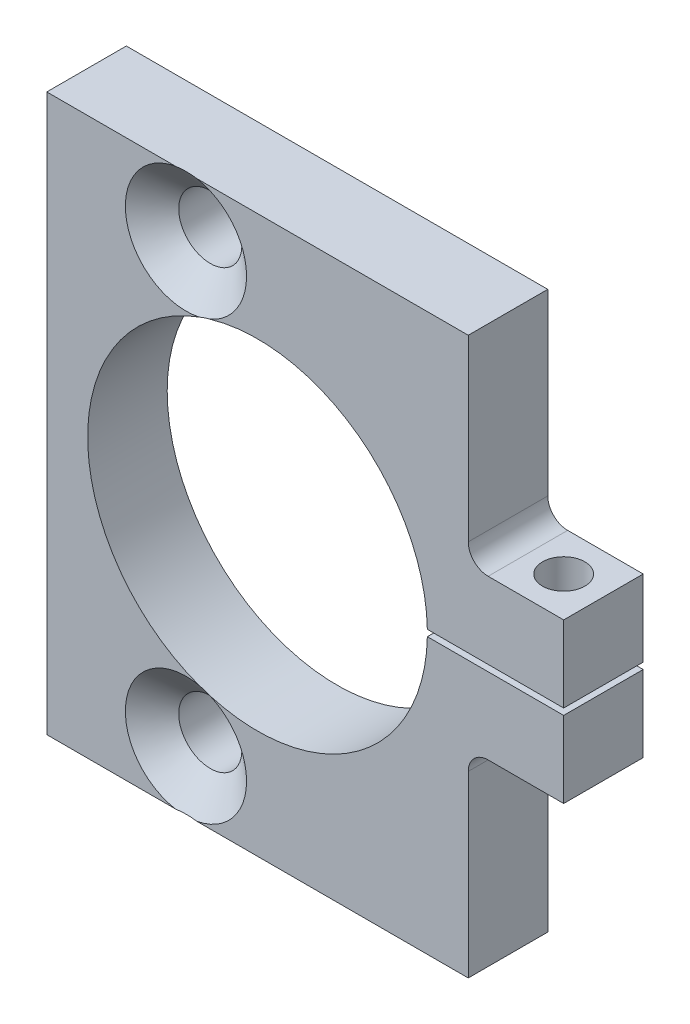
SolidWorks part; units mm, degrees
material "6061-T6 (SS)"
ref_plane "Front Plane" through (0, 0, 0) normal (0, 0, 1) x (1, 0, 0)
ref_plane "Top Plane" through (0, 0, 0) normal (0, 1, 0) x (1, 0, 0)
ref_plane "Right Plane" through (0, 0, 0) normal (1, 0, 0) x (0, 0, -1)
sketch "Sketch1" plane through (0, 0, 0) normal (0, 0, 1) x (1, 0, 0)
  line L1 (-41.275, -44.45) -> (41.275, -44.45)
  line L2 (-41.275, -44.45) -> (-41.275, 44.45)
  line L3 (-41.275, 44.45) -> (41.275, 44.45)
  line L4 (41.275, -44.45) -> (41.275, 44.45)
  line L5 (-41.275, -44.45) -> (41.275, 44.45) construction
  line L6 (-41.275, 44.45) -> (41.275, -44.45) construction
  point P0 (0, 0)
  dimension "D1" = 82.55
  dimension "D2" = 88.9
extrude "Extrude1" add sketch "Sketch1" along normal blind 12.7
sketch "Sketch2" plane through (0, 0, 12.7) normal (0, 0, 1) x (1, 0, 0)
  line L0 (-41.275, 0) -> (-7.62, 0) construction
  line L4 (-41.275, 44.45) -> (-41.275, -44.45) construction
  circle A0 centre (-7.62, 0) radius 27.1272
  dimension "D1" = 54.2544
  dimension "D2" = 33.655
extrude "Extrude2" cut sketch "Sketch2" against normal through all
sketch "Sketch3" plane through (0, 0, 12.7) normal (0, 0, 1) x (1, 0, 0)
  line L0 (19.5072, 0) -> (41.275, 0) construction
  line L1 (41.275, -44.45) -> (41.275, 44.45) construction
  line L3 (16.1568, -0.508) -> (44.6254, -0.508)
  line L4 (16.1568, -0.508) -> (16.1568, 0.508)
  line L5 (16.1568, 0.508) -> (44.6254, 0.508)
  line L6 (44.6254, -0.508) -> (44.6254, 0.508)
  line L7 (16.1568, -0.508) -> (44.6254, 0.508) construction
  line L8 (16.1568, 0.508) -> (44.6254, -0.508) construction
  circle A0 centre (-7.62, 0) radius 27.1272 construction
  point P6 (30.3911, 0)
  dimension "D1" = 1.016
extrude "Extrude3" cut sketch "Sketch3" against normal through all
sketch "Sketch4" plane through (0, 44.45, 0) normal (0, 1, 0) x (1, 0, 0)
  line L0 (41.275, -6.35) -> (34.925, -6.35) construction
  line L1 (41.275, -12.7) -> (41.275, 0) construction
  dimension "D1" = 6.35
hole_wizard "1/4 Clearance Hole1" positions "3DSketch1" profile "Sketch5" hole size "1/4" standard "Ansi Inch" end condition through all
sketch3d "3DSketch1"
  point P0 (34.925, 44.45, 6.35)
sketch "Sketch5" plane through (34.925, 44.45, 6.35) normal (1, 0, 0) x (0, 0, 1)
  line L0 (0, 0) -> (0, 88.9)
  line L1 (0, 88.9) -> (3.3782, 88.9)
  line L2 (3.3782, 88.9) -> (3.3782, 0)
  line L5 (3.3782, 0) -> (0, 0)
  line L11 (0, -6.35) -> (0, 107.95) construction
  dimension "Thru Hole Dia." = 6.7564
  dimension "Thru Hole Depth" = 88.9
sketch "Sketch8" plane through (0, 0, 12.7) normal (0, 0, 1) x (1, 0, 0)
  line L0 (-41.275, 34.925) -> (-19.05, 34.925) construction
  line L1 (-41.275, 44.45) -> (-41.275, -44.45) construction
  line L2 (41.275, 44.45) -> (-41.275, 44.45) construction
  dimension "D1" = 22.225
  dimension "D2" = 9.525
hole_wizard "CSK for 3/8 Flat Head Machine Screw (100)1" positions "3DSketch3" profile "Sketch9" countersink size "3/8" standard "Ansi Inch"
sketch3d "3DSketch3"
  point P0 (-19.05, 34.925, 12.7)
sketch "Sketch9" plane through (-19.05, 34.925, 12.7) normal (1, 0, 0) x (0, -1, 0)
  line L0 (0, 0) -> (0, 14.4595)
  line L1 (0, 14.4595) -> (5.0419, 11.43)
  line L2 (5.0419, 11.43) -> (5.0419, 3.8896)
  line L3 (5.0419, 3.8896) -> (9.6774, 0)
  line L5 (9.6774, 0) -> (0, 0)
  line L6 (-5.0419, 3.8896) -> (-9.6774, 0) construction
  line L10 (0, 14.4595) -> (-5.0419, 11.43) construction
  line L11 (0, -6.35) -> (0, 107.95) construction
  dimension "Hole Dia." = 10.0838
  dimension "Hole Depth" = 11.43
  dimension "Near C'Sink Dia." = 19.3548
  dimension "Near C'Sink Angle" = 100
  dimension "Drill Angle" = 118
mirror "Mirror1" about plane through (0, 0, 0) normal (0, 1, 0) of "CSK for 3/8 Flat Head Machine Screw (100)1"
sketch "Sketch10" plane through (0, 0, 12.7) normal (0, 0, 1) x (1, 0, 0)
  line L1 (41.275, 44.45) -> (26.035, 44.45)
  line L2 (41.275, 44.45) -> (41.275, 12.7)
  line L3 (41.275, 12.7) -> (26.035, 12.7)
  line L4 (26.035, 44.45) -> (26.035, 12.7)
  dimension "D1" = 15.24
  dimension "D2" = 31.75
extrude "Extrude4" cut sketch "Sketch10" against normal through all
mirror "Mirror2" about plane through (0, 0, 0) normal (0, 1, 0) of "Extrude4"
fillet "Fillet1" radius 3.175 2 edges at (26.035, -12.7, 6.35) (26.035, 12.7, 6.35)
